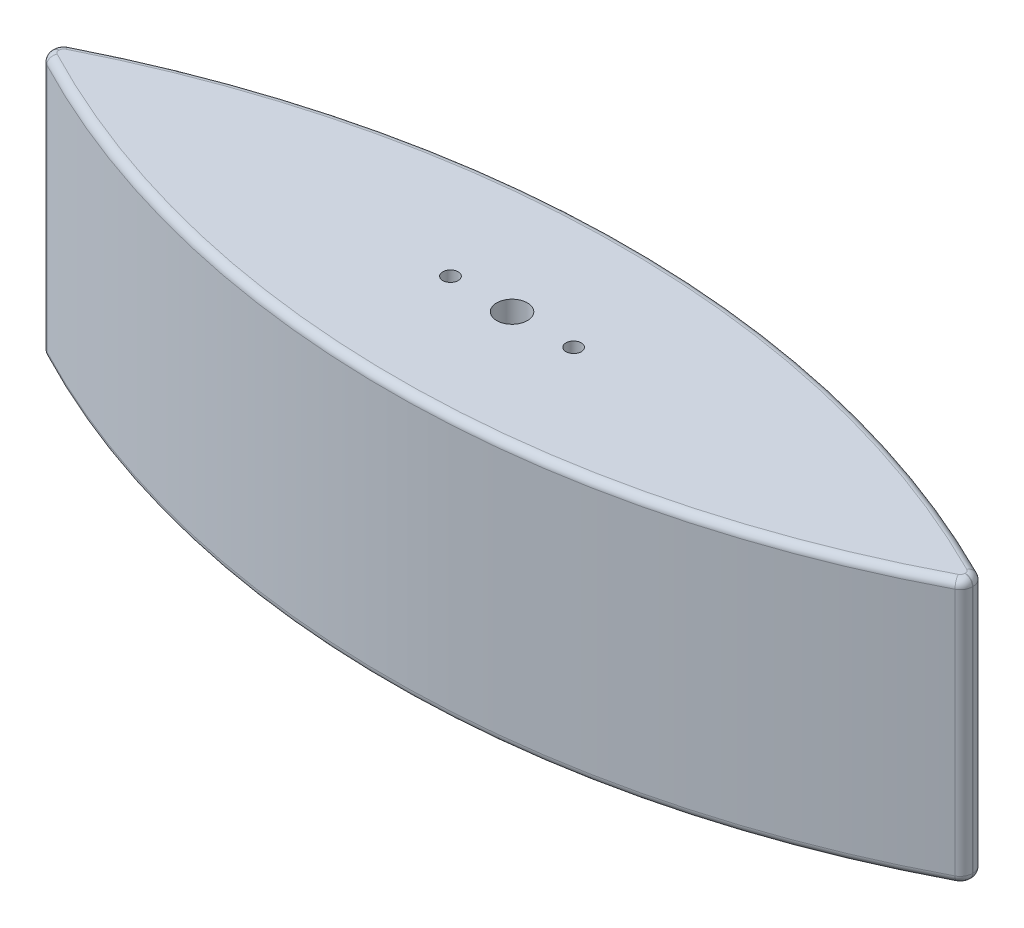
SolidWorks part; units mm, degrees
ref_plane "Front Plane" through (0, 0, 0) normal (0, 0, 1) x (1, 0, 0)
ref_plane "Top Plane" through (0, 0, 0) normal (0, 1, 0) x (1, 0, 0)
ref_plane "Right Plane" through (0, 0, 0) normal (1, 0, 0) x (0, 0, -1)
sketch "Sketch1" plane through (0, 0, 0) normal (0, 0, 1) x (1, 0, 0)
  line L1 (0, 165.1431) -> (190.0499, 165.1431)
  line L2 (0, 165.1431) -> (0, 219.5271)
  line L3 (0, 219.5271) -> (190.0499, 219.5271)
  line L4 (190.0499, 165.1431) -> (190.0499, 219.5271)
extrude "Boss-Extrude1" add sketch "Sketch1" along normal blind 28.575 and the other way blind 28.575
sketch "Sketch2" plane through (0, 219.5271, 0) normal (0, 1, 0) x (1, 0, 0)
  line L1 (0, 28.575) -> (0, -28.575) construction
  line L2 (190.0499, 28.575) -> (190.0499, -28.575) construction
  line L3 (190.0499, 28.575) -> (190.0499, -28.575) construction
  line L4 (0, 1.5875) -> (0, -1.5875)
  line L5 (190.0499, 1.5875) -> (190.0499, -1.5875)
  line L7 (-10.9652, 42.0843) -> (199.4564, 42.0843)
  line L8 (-10.9652, 42.0843) -> (-10.9652, -43.8378)
  line L9 (-10.9652, -43.8378) -> (199.4564, -43.8378)
  line L10 (199.4564, 42.0843) -> (199.4564, -43.8378)
  arc A0 (0, 1.5875) -> (190.0499, 1.5875) centre (95.025, -184.1124) cw
  arc A1 (0, -1.5875) -> (190.0499, -1.5875) centre (95.025, 177.0281) ccw
  point P13 (190.0499, 0)
  dimension "D1" = 1.5875
  dimension "D2" = 1.5875
  dimension "D3" = 1.5875
  dimension "D4" = 1.5875
extrude "Cut-Extrude1" cut sketch "Sketch2" against normal through all
sketch "Sketch3" plane through (0, 219.5271, 0) normal (0, 1, 0) x (1, 0, 0)
  line L0 (0, 0) -> (190.0499, 0)
  line L1 (190.0499, 1.5875) -> (190.0499, -1.5875) construction
  circle A0 centre (95.025, 0) radius 3.175
  dimension "D1" = 6.35
extrude "Cut-Extrude2" cut sketch "Sketch3" against normal through all contours A0
fillet "Fillet1" radius 2.54 4 edges at (190.0499, 192.3351, -1.5875) (190.0499, 192.3351, 1.5875) (0, 192.3351, -1.5875) (0, 192.3351, 1.5875)
fillet "Fillet2" radius 1.5875 16 edges at (0.3676, 165.1431, 1.3714) (0, 165.1431, 0.0138) (0.3781, 165.1431, -1.3609) (95.025, 165.1431, -24.4882) (189.6718, 165.1431, -1.3609) (190.0499, 165.1431, 0.0138) (189.6823, 165.1431, 1.3714) (0.3676, 219.5271, 1.3714) (0, 219.5271, 0.0138) (0.3781, 219.5271, -1.3609) (95.025, 219.5271, -24.4882) (189.6718, 219.5271, -1.3609) (190.0499, 219.5271, 0.0138) (189.6823, 219.5271, 1.3714) (95.025, 165.1431, 25.2916) (95.025, 219.5271, 25.2916)
sketch "Sketch4" plane through (0, 219.5271, 0) normal (0, 1, 0) x (1, 0, 0)
  circle A0 centre (107.725, 0) radius 1.5875
  circle A1 centre (82.325, 0) radius 1.5875
  circle A2 centre (95.025, 0) radius 3.175 construction
  dimension "D2" = 12.7
  dimension "D3" = 3.175
  dimension "D1" = 12.7
extrude "Cut-Extrude3" cut sketch "Sketch4" against normal blind 12.7
sketch "Sketch5" plane through (0, 165.1431, 0) normal (0, -1, 0) x (1, 0, 0)
  circle A0 centre (82.325, 0) radius 1.5875
  circle A1 centre (107.725, 0) radius 1.5875
  circle A2 centre (95.025, 0) radius 3.175 construction
  dimension "D1" = 12.7
  dimension "D2" = 12.7
  dimension "D3" = 3.175
extrude "Cut-Extrude4" cut sketch "Sketch5" against normal blind 12.7
